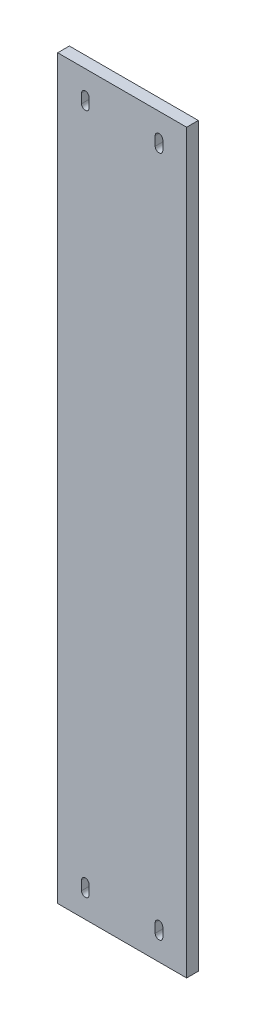
SolidWorks part; units mm, degrees
ref_plane "Front Plane" through (0, 0, 0) normal (0, 0, 1) x (1, 0, 0)
ref_plane "Top Plane" through (0, 0, 0) normal (0, 1, 0) x (1, 0, 0)
ref_plane "Right Plane" through (0, 0, 0) normal (1, 0, 0) x (0, 0, -1)
sketch "Sketch1" plane through (0, 0, 0) normal (0, 0, 1) x (1, 0, 0)
  line L0 (0, 200) -> (0, -200) construction
  line L1 (-35, -200) -> (35, -200)
  line L2 (-35, -200) -> (-35, 200)
  line L3 (-35, 200) -> (35, 200)
  line L4 (35, -200) -> (35, 200)
  line L5 (-35, -200) -> (35, 200) construction
  line L6 (-35, 200) -> (35, -200) construction
  line L7 (-35, 0) -> (35, 0) construction
  line L8 (-35, 185) -> (0, 185) construction
  line L9 (-20, 182.5) -> (-20, 187.5) construction
  line L10 (-22.05, 182.5) -> (-22.05, 187.5)
  line L11 (-17.95, 182.5) -> (-17.95, 187.5)
  line L12 (20, 182.5) -> (20, 187.5) construction
  line L13 (22.05, 182.5) -> (22.05, 187.5)
  line L14 (17.95, 182.5) -> (17.95, 187.5)
  line L15 (-20, -182.5) -> (-20, -187.5) construction
  line L16 (-22.05, -182.5) -> (-22.05, -187.5)
  line L17 (-17.95, -182.5) -> (-17.95, -187.5)
  line L18 (20, -182.5) -> (20, -187.5) construction
  line L19 (22.05, -182.5) -> (22.05, -187.5)
  line L20 (17.95, -182.5) -> (17.95, -187.5)
  circle A0 centre (-20, 185) radius 2.05 construction
  arc A1 (-22.05, 182.5) -> (-17.95, 182.5) centre (-20, 182.5) ccw
  arc A2 (-17.95, 187.5) -> (-22.05, 187.5) centre (-20, 187.5) ccw
  arc A3 (22.05, 182.5) -> (17.95, 182.5) centre (20, 182.5) cw
  arc A4 (17.95, 187.5) -> (22.05, 187.5) centre (20, 187.5) cw
  arc A5 (-22.05, -182.5) -> (-17.95, -182.5) centre (-20, -182.5) cw
  arc A6 (-17.95, -187.5) -> (-22.05, -187.5) centre (-20, -187.5) cw
  arc A7 (22.05, -182.5) -> (17.95, -182.5) centre (20, -182.5) ccw
  arc A8 (17.95, -187.5) -> (22.05, -187.5) centre (20, -187.5) ccw
  point P0 (0, 0)
  point P16 (-20, 185)
  point P21 (0, 0)
  point P24 (20, 185)
  point P31 (-20, -185)
  point P38 (20, -185)
  dimension "D4" = 4.1
  dimension "D6" = 2.05
  dimension "D1" = 400
  dimension "D2" = 70
  dimension "D3" = 15
  dimension "D5" = 5
  dimension "D13" = 15
extrude "Boss-Extrude1" add sketch "Sketch1" along normal blind 6.35
